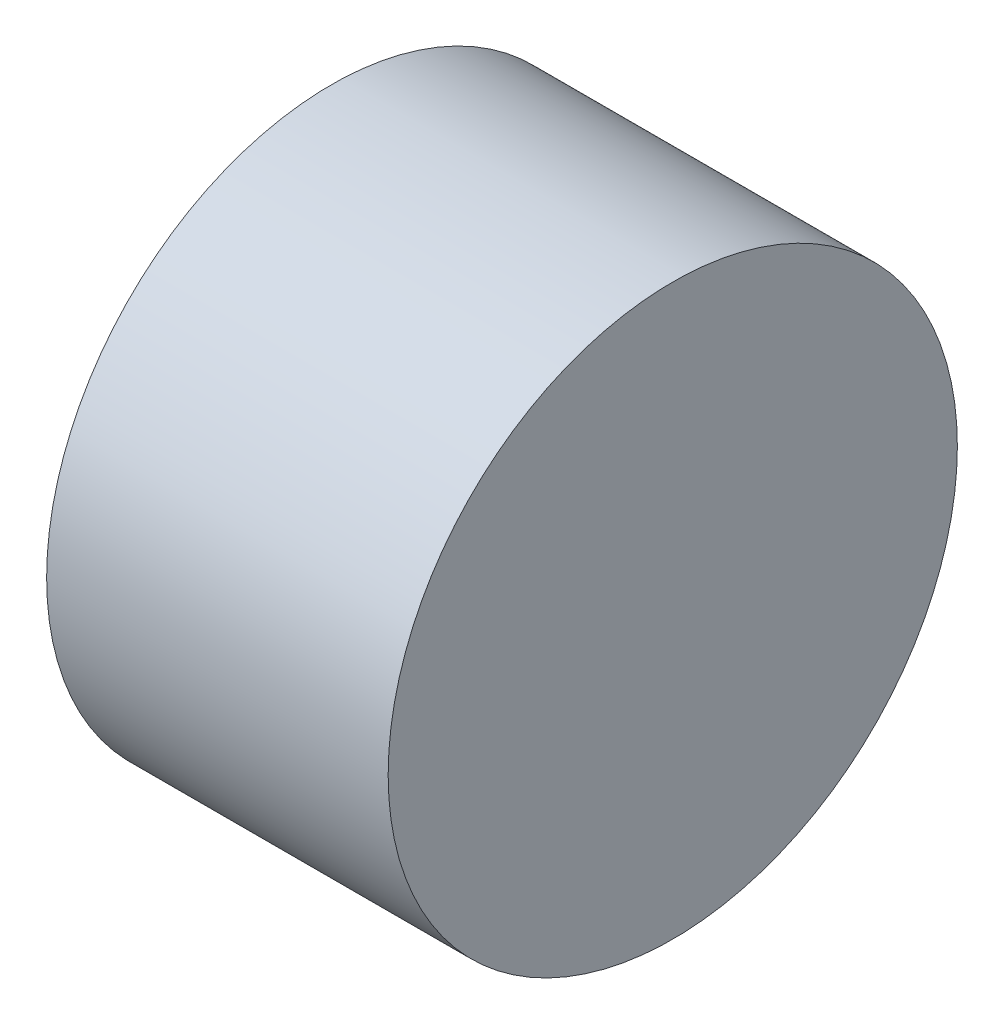
SolidWorks part; units mm, degrees
material "自定义塑料"
ref_plane "前视基准面" through (0, 0, 0) normal (0, 0, 1) x (1, 0, 0)
ref_plane "上视基准面" through (0, 0, 0) normal (0, 1, 0) x (1, 0, 0)
ref_plane "右视基准面" through (0, 0, 0) normal (1, 0, 0) x (0, 0, -1)
sketch "草图1" plane through (0, 0, 0) normal (1, 0, 0) x (0, 0, -1)
  circle A0 centre (0, 0) radius 50
  dimension "D1" = 100
extrude "凸台-拉伸1" add sketch "草图1" along normal blind 30 and the other way blind 30
